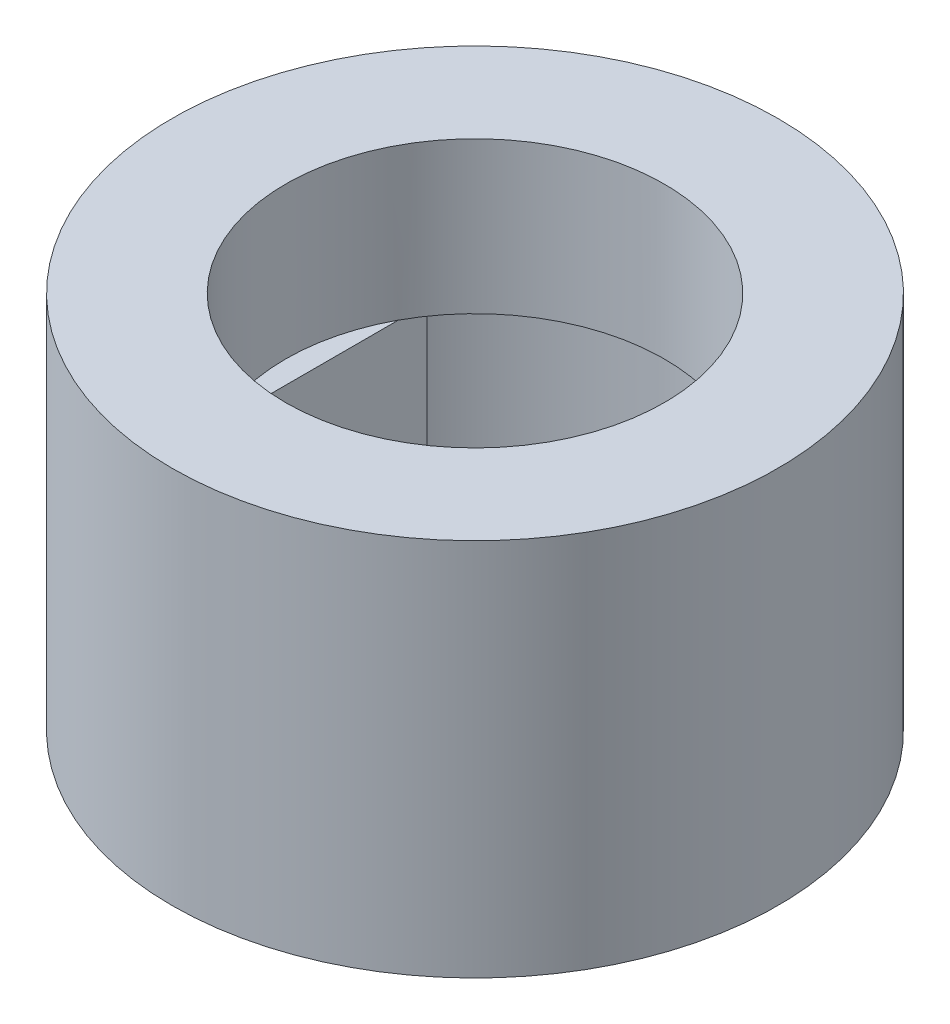
SolidWorks part; units mm, degrees
ref_plane "Front Plane" through (0, 0, 0) normal (0, 0, 1) x (1, 0, 0)
ref_plane "Top Plane" through (0, 0, 0) normal (0, 1, 0) x (1, 0, 0)
ref_plane "Right Plane" through (0, 0, 0) normal (1, 0, 0) x (0, 0, -1)
sketch "Sketch1" plane through (0, 0, 0) normal (0, 1, 0) x (1, 0, 0)
  circle A0 centre (0, 0) radius 5.08
  dimension "D1" = 10.16
extrude "Boss-Extrude1" add sketch "Sketch1" along normal blind 6.35
sketch "Sketch2" plane through (0, 0, 0) normal (0, 1, 0) x (1, 0, 0)
  line L0 (-2.794, -1.9879) -> (-2.794, 1.9879)
  line L1 (0, 0) -> (-2.794, 0) construction
  circle A0 centre (0, 0) radius 3.429
  dimension "D1" = 6.858
  dimension "D2" = 2.794
extrude "Cut-Extrude1" cut sketch "Sketch2" along normal blind 3.81 contours L0 A0 region at (0.1487, 0, 0)
sketch "Sketch3" plane through (0, 6.35, 0) normal (0, 1, 0) x (1, 0, 0)
  circle A0 centre (0, 0) radius 3.175
  dimension "D1" = 6.35
extrude "Cut-Extrude2" cut sketch "Sketch3" against normal blind 2.54
